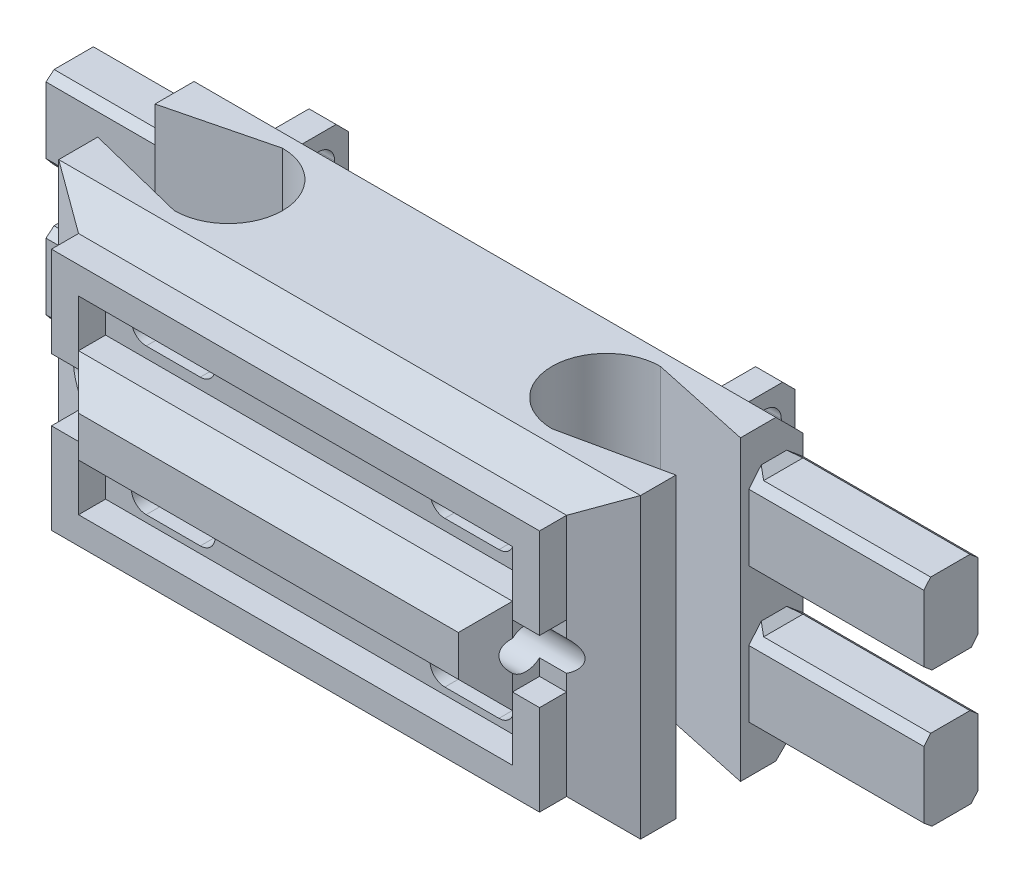
SolidWorks part; units mm, degrees
ref_plane "Front Plane" through (0, 0, 0) normal (0, 0, 1) x (1, 0, 0)
ref_plane "Top Plane" through (0, 0, 0) normal (0, 1, 0) x (1, 0, 0)
ref_plane "Right Plane" through (0, 0, 0) normal (1, 0, 0) x (0, 0, -1)
sketch "Base" plane through (0, 0, 0) normal (0, 0, 1) x (1, 0, 0)
  line L1 (0, 0) -> (21.5, 0)
  line L2 (0, 0) -> (0, 11)
  line L3 (0, 11) -> (21.5, 11)
  line L4 (21.5, 0) -> (21.5, 11)
  dimension "D1" = 21.5
  dimension "D2" = 11
extrude "Boss-Extrude1" add sketch "Base" along normal blind 7
chamfer "Chamfer4" distance 1 angle 45 2 edges at (10.75, 11, 7) (10.75, 0, 7)
chamfer "Chamfer5" distance 1 angle 60 2 edges at (0, 5.5, 7) (21.5, 5.5, 7)
chamfer "Chamfer6" distance 1 angle 45 2 edges at (10.75, 11, 0) (10.75, 0, 0)
sketch "Tendon extrude" plane through (0, 0, 0) normal (0, -1, 0) x (1, 0, 0)
  line L0 (10.75, 6) -> (10.75, -3.9632) construction
  line L1 (21.5, 6) -> (0, 6) construction
  line L2 (0, 3.5) -> (21.7648, 3.5) construction
  line L3 (0, 6) -> (0, 1) construction
  line L4 (3.77, 3.5) -> (-2.23, 3.5) construction
  line L5 (-2.23, 3) -> (-2.23, 4)
  line L6 (3.77, 5.5) -> (-2.23, 4)
  line L7 (-2.23, 3) -> (3.77, 1.5)
  line L10 (17.73, 3.5) -> (24.73, 3.5) construction
  line L11 (24.73, 3) -> (24.73, 4)
  line L12 (17.73, 5.5) -> (24.73, 4)
  line L13 (24.73, 3) -> (17.73, 1.5)
  circle A0 centre (3.77, 3.5) radius 2
  circle A1 centre (17.73, 3.5) radius 2
  dimension "D1" = 4
  dimension "D2" = 3.77
  dimension "D3" = 1
  dimension "D4" = 6
  dimension "D5" = 1
  dimension "D6" = 7
sketch "Sketch8" plane through (0, 0, 7) normal (0, 0, 1) x (1, 0, 0)
  line L0 (19.7679, 5.5) -> (1.7321, 5.5) construction
  line L1 (19.7679, 1) -> (19.7679, 10) construction
  line L2 (1.7321, 10) -> (1.7321, 1) construction
  line L3 (10.75, 1) -> (10.75, 10) construction
  line L4 (1.7321, 1) -> (19.7679, 1) construction
  line L5 (19.7679, 10) -> (1.7321, 10) construction
  line L6 (2.7321, 3.75) -> (2.7321, 7.25)
  line L7 (18.7679, 7.25) -> (2.7321, 7.25)
  line L8 (18.7679, 7.25) -> (18.7679, 3.75)
  line L9 (18.7679, 3.75) -> (2.7321, 3.75)
  point P17 (2.7321, 5.5)
  point P18 (18.7679, 5.5)
  dimension "D1" = 1.75
  dimension "D2" = 1
  dimension "D3" = 1
extrude "Boss-Extrude5" add sketch "Sketch8" along normal blind 2
sketch "Sketch9" plane through (18.7679, 0, 0) normal (1, 0, 0) x (0, 0, -1)
  line L0 (-9, 5.5) -> (-7, 5.5) construction
  line L1 (-9, 3.75) -> (-9, 7.25) construction
  line L2 (-7, 3.75) -> (-7, 7.25) construction
  circle A0 centre (-7.5, 5.5) radius 0.75
  dimension "D1" = 1.5
  dimension "D2" = 1.5
extrude "Cut-Extrude5" cut sketch "Sketch9" against normal blind 34.5 and the other way blind 4.2544
chamfer "Chamfer9" distance 1 angle 45 4 edges at (2.7321, 5.5, 9) (10.75, 7.25, 9) (18.7679, 5.5, 9) (10.75, 3.75, 9)
sketch "Sketch13" plane through (0, 0, 0) normal (0, 0, -1) x (-1, 0, 0)
  line L0 (0, 5.5) -> (-33.4926, 5.5) construction
  line L1 (0, 10) -> (0, 1) construction
  line L2 (-10.75, 1) -> (-10.75, 15.915) construction
  line L3 (-21.5, 1) -> (0, 1) construction
  line L4 (-1, 7.25) -> (-5.75, 7.25)
  line L5 (-15.75, 7.25) -> (-15.75, 3.75)
  line L6 (-1, 7.25) -> (-1, 3.75)
  line L7 (-1, 3.75) -> (-5.75, 3.75)
  line L8 (-5.75, 7.25) -> (-5.75, 3.75)
  line L9 (-20.5, 7.25) -> (-15.75, 7.25)
  line L10 (-20.5, 3.75) -> (-15.75, 3.75)
  line L11 (-20.5, 7.25) -> (-20.5, 3.75)
  point P13 (-5.75, 5.5)
  point P14 (-1, 5.5)
  dimension "D1" = 1.75
  dimension "D2" = 1
  dimension "D3" = 5
extrude "Boss-Extrude6" add sketch "Sketch13" along normal blind 2
chamfer "Chamfer10" distance 1 angle 45 8 edges at (15.75, 5.5, -2) (18.125, 3.75, -2) (20.5, 5.5, -2) (18.125, 7.25, -2) (3.375, 7.25, -2) (1, 5.5, -2) (3.375, 3.75, -2) (5.75, 5.5, -2)
sketch "Sketch14" plane through (1, 0, 0) normal (-1, 0, 0) x (0, 0, 1)
  line L0 (-1, 5.5) -> (0, 5.5) construction
  line L1 (-1, 7.25) -> (-1, 3.75) construction
  line L2 (0, 3.75) -> (0, 7.25) construction
  line L3 (-2, 4.75) -> (-2, 6.25) construction
  circle A0 centre (-0.5, 5.5) radius 0.75
  dimension "D1" = 1.5
  dimension "D2" = 1.5
extrude "Cut-Extrude6" cut sketch "Sketch14" against normal blind 30 and the other way blind 3
sketch "Sketch15" plane through (0, 0, 0) normal (0, 0, -1) x (-1, 0, 0)
  line L0 (-19.5, 4.75) -> (-16.75, 4.75) construction
  line L1 (-19.5, 1) -> (-18.5, 1)
  line L2 (-19.5, 1) -> (-19.5, 4.75)
  line L3 (-19.5, 4.75) -> (-18.5, 4.75)
  line L4 (-18.5, 1) -> (-18.5, 4.75)
  line L5 (-19.5, 6.25) -> (-19.5, 4.75) construction
  line L6 (-10.75, 1) -> (-10.75, 10) construction
  line L7 (-21.5, 1) -> (0, 1) construction
  line L8 (0, 10) -> (-21.5, 10) construction
  line L9 (-16.75, 6.25) -> (-19.5, 6.25) construction
  line L10 (-19.5, 6.25) -> (-18.5, 6.25)
  line L11 (-19.5, 6.25) -> (-19.5, 10)
  line L12 (-19.5, 10) -> (-18.5, 10)
  line L13 (-18.5, 6.25) -> (-18.5, 10)
  line L14 (-2, 1) -> (-3, 1)
  line L15 (-2, 1) -> (-2, 4.75)
  line L16 (-3, 1) -> (-3, 4.75)
  line L17 (-2, 4.75) -> (-3, 4.75)
  line L18 (-2, 6.25) -> (-3, 6.25)
  line L19 (-2, 10) -> (-3, 10)
  line L20 (-3, 6.25) -> (-3, 10)
  line L21 (-2, 6.25) -> (-2, 10)
  dimension "D1" = 0
  dimension "D3" = 1
  dimension "D4" = 0
  dimension "D5" = 0
extrude "Boss-Extrude7" add sketch "Sketch15" along normal blind 2
sketch "Sketch16" plane through (19.5, 0, 0) normal (1, 0, 0) x (0, 0, -1)
  line L0 (0.6, 3.15) -> (0.6, 2.15) construction
  line L1 (1.2, 3.15) -> (1.2, 2.15)
  line L2 (0, 3.15) -> (0, 2.15)
  line L3 (1, 3.75) -> (0, 3.75) construction
  line L5 (0.6, 7.85) -> (0.6, 8.85) construction
  line L6 (0, 7.85) -> (0, 8.85)
  line L7 (1.2, 7.85) -> (1.2, 8.85)
  line L9 (1, 7.25) -> (0, 7.25) construction
  line L10 (0, 3.75) -> (0, 1) construction
  arc A0 (1.2, 3.15) -> (0, 3.15) centre (0.6, 3.15) ccw
  arc A1 (0, 2.15) -> (1.2, 2.15) centre (0.6, 2.15) ccw
  arc A2 (0, 7.85) -> (1.2, 7.85) centre (0.6, 7.85) ccw
  arc A3 (1.2, 8.85) -> (0, 8.85) centre (0.6, 8.85) ccw
  point P2 (0.6, 2.65)
  point P13 (0.6, 8.35)
  point P20 (0.5, 7.25)
  dimension "D1" = 1
  dimension "D2" = 0.6
  dimension "D3" = 0.6
  dimension "D4" = 0
  dimension "D5" = 0.6
extrude "Cut-Extrude7" cut sketch "Sketch16" against normal blind 26
chamfer "Chamfer11" distance 0.3 angle 45 8 edges at (2, 2.875, -2) (3, 2.875, -2) (3, 8.125, -2) (2, 8.125, -2) (19.5, 8.125, -2) (18.5, 8.125, -2) (19.5, 2.875, -2) (18.5, 2.875, -2)
chamfer "Chamfer12" distance 0.75 angle 45 4 edges at (19, 1, -2) (19, 10, -2) (2.5, 10, -2) (2.5, 1, -2)
extrude "Cut-Extrude8" cut sketch "Tendon extrude" against normal up to surface (11 mm away)
sketch "Sketch18" plane through (21.5, 0, 0) normal (1, 0, 0) x (0, 0, -1)
  line L0 (-2.3079, 5.5) -> (-0.25, 5.5) construction
  line L1 (-2.3079, 11) -> (-2.3079, 0) construction
  line L3 (-2, 6.5) -> (0, 6.5)
  line L4 (-2, 6.5) -> (-2, 9.5)
  line L5 (-2, 9.5) -> (0, 9.5)
  line L6 (0, 6.5) -> (0, 9.5)
  line L7 (-2, 4.5) -> (0, 4.5)
  line L8 (0, 4.5) -> (0, 1.5)
  line L9 (-2, 1.5) -> (0, 1.5)
  line L10 (-2, 4.5) -> (-2, 1.5)
  line L11 (0, 6.059) -> (0, 10) construction
  arc A0 (0, 6.059) -> (0, 4.941) centre (0.5, 5.5) ccw construction
  dimension "D1" = 3
  dimension "D2" = 2
  dimension "D3" = 1
extrude "Boss-Extrude8" add sketch "Sketch18" along normal blind 6.47
chamfer "Chamfer13" distance 0.25 angle 50 8 edges at (24.735, 1.5, 2) (24.735, 4.5, 2) (24.735, 6.5, 2) (24.735, 9.5, 2) (24.735, 9.5, 0) (24.735, 6.5, 0) (24.735, 4.5, 0) (24.735, 1.5, 0)
chamfer "Chamfer14" distance 0.25 angle 50 4 edges at (21.5, 9.5, 1.024) (21.5, 1.5, 0.976) (21.5, 4.5, 1.024) (21.5, 6.5, 0.976)
sketch "Sketch19" plane through (0, 0, 0) normal (-1, 0, 0) x (0, 0, 1)
  line L0 (0.25, 5.5) -> (2.4425, 5.5) construction
  line L1 (2.4425, 11) -> (2.4425, 0) construction
  line L3 (0, 4.5) -> (2, 4.5)
  line L4 (0, 4.5) -> (0, 1.5)
  line L5 (0, 1.5) -> (2, 1.5)
  line L6 (2, 4.5) -> (2, 1.5)
  line L7 (2, 6.5) -> (2, 9.5)
  line L8 (0, 9.5) -> (2, 9.5)
  line L9 (0, 6.5) -> (0, 9.5)
  line L10 (0, 6.5) -> (2, 6.5)
  line L11 (0, 4.941) -> (0, 1) construction
  arc A0 (0, 4.941) -> (0, 6.059) centre (-0.5, 5.5) ccw construction
  dimension "D1" = 2
  dimension "D2" = 3
  dimension "D4" = 1
extrude "Boss-Extrude9" add sketch "Sketch19" along normal blind 4.47
chamfer "Chamfer15" distance 0.25 angle 50 8 edges at (-2.235, 1.5, 2) (-2.235, 4.5, 2) (-2.235, 9.5, 2) (-2.235, 6.5, 2) (-2.235, 1.5, 0) (-2.235, 4.5, 0) (-2.235, 9.5, 0) (-2.235, 6.5, 0)
chamfer "Chamfer16" distance 0.25 angle 50 4 edges at (0, 9.5, 0.976) (0, 6.5, 1.024) (0, 4.5, 0.976) (0, 1.5, 1.024)
sketch "Sketch20" plane through (0, 0, 7) normal (0, 0, 1) x (1, 0, 0)
  line L0 (19.7679, 6.059) -> (19.7679, 10) construction
  line L1 (1.7321, 10) -> (19.7679, 10)
  line L2 (1.7321, 10) -> (1.7321, 9)
  line L3 (1.7321, 9) -> (19.7679, 9)
  line L4 (19.7679, 10) -> (19.7679, 9)
  line L5 (2.7321, 7.25) -> (2.7321, 6.059) construction
  line L6 (2.7321, 6.6545) -> (1.7321, 6.6545)
  line L7 (2.7321, 6.6545) -> (2.7321, 9)
  line L8 (2.7321, 9) -> (1.7321, 9)
  line L9 (1.7321, 6.6545) -> (1.7321, 9)
  line L10 (18.7679, 6.059) -> (18.7679, 7.25) construction
  line L11 (18.7679, 6.6545) -> (19.7679, 6.6545)
  line L12 (18.7679, 6.6545) -> (18.7679, 9)
  line L13 (18.7679, 9) -> (19.7679, 9)
  line L14 (19.7679, 6.6545) -> (19.7679, 9)
  line L15 (1.7321, 4.941) -> (1.7321, 1) construction
  line L16 (19.7679, 1) -> (1.7321, 1)
  line L17 (19.7679, 1) -> (19.7679, 2)
  line L18 (19.7679, 2) -> (1.7321, 2)
  line L19 (1.7321, 1) -> (1.7321, 2)
  line L20 (2.7321, 4.941) -> (2.7321, 3.75) construction
  line L21 (2.7321, 4.3455) -> (1.7321, 4.3455)
  line L22 (2.7321, 4.3455) -> (2.7321, 2)
  line L23 (2.7321, 2) -> (1.7321, 2)
  line L24 (1.7321, 4.3455) -> (1.7321, 2)
  line L25 (18.7679, 3.75) -> (18.7679, 4.941) construction
  line L26 (19.7679, 2) -> (18.7679, 2)
  line L27 (19.7679, 2) -> (19.7679, 4.3455)
  line L28 (19.7679, 4.3455) -> (18.7679, 4.3455)
  line L29 (18.7679, 2) -> (18.7679, 4.3455)
  line M2 (19.7679, 6.059) -> (19.7679, 10)
  line M3 (19.7679, 10) -> (1.7321, 10)
  line M4 (1.7321, 10) -> (1.7321, 6.059)
  line M6 (2.7321, 6.059) -> (2.7321, 7.25)
  line M8 (18.7679, 7.25) -> (18.7679, 6.059)
extrude "Boss-Extrude10" add sketch "Sketch20" along normal blind 1 contours L7 L3 L6 M6 M4 | L3 M4 M2 M3 | L12 L11 L3 M8 M2 | L29 L18 L27 L28 | L19 L16 L17 L18 | L21 L24 L18 L22
sketch "Sketch21" plane through (0, 0, 7) normal (0, 0, 1) x (1, 0, 0)
  line L0 (4.2321, 8.2) -> (6.2321, 8.2) construction
  line L1 (4.2321, 8.7469) -> (6.2321, 8.7469)
  line L2 (4.2321, 7.6531) -> (6.2321, 7.6531)
  line L3 (15.2679, 8.2) -> (17.2679, 8.2) construction
  line L4 (15.2679, 8.7469) -> (17.2679, 8.7469)
  line L5 (15.2679, 7.6531) -> (17.2679, 7.6531)
  line L6 (15.2679, 2.8) -> (17.2679, 2.8) construction
  line L7 (15.2679, 3.3469) -> (17.2679, 3.3469)
  line L8 (15.2679, 2.2531) -> (17.2679, 2.2531)
  line L9 (6.2321, 2.8) -> (4.2321, 2.8) construction
  line L10 (6.2321, 2.2531) -> (4.2321, 2.2531)
  line L11 (6.2321, 3.3469) -> (4.2321, 3.3469)
  line L12 (2.7321, 9) -> (18.7679, 9) construction
  line L13 (18.7679, 2) -> (2.7321, 2) construction
  line L14 (2.7321, 7.25) -> (2.7321, 9) construction
  line L15 (18.7679, 7.25) -> (18.7679, 9) construction
  arc A0 (4.2321, 8.7469) -> (4.2321, 7.6531) centre (4.2321, 8.2) ccw
  arc A1 (6.2321, 7.6531) -> (6.2321, 8.7469) centre (6.2321, 8.2) ccw
  arc A2 (15.2679, 8.7469) -> (15.2679, 7.6531) centre (15.2679, 8.2) ccw
  arc A3 (17.2679, 7.6531) -> (17.2679, 8.7469) centre (17.2679, 8.2) ccw
  arc A4 (15.2679, 3.3469) -> (15.2679, 2.2531) centre (15.2679, 2.8) ccw
  arc A5 (17.2679, 2.2531) -> (17.2679, 3.3469) centre (17.2679, 2.8) ccw
  arc A6 (6.2321, 2.2531) -> (6.2321, 3.3469) centre (6.2321, 2.8) ccw
  arc A7 (4.2321, 3.3469) -> (4.2321, 2.2531) centre (4.2321, 2.8) ccw
  point P2 (5.2321, 8.2)
  point P7 (16.2679, 8.2)
  point P14 (16.2679, 2.8)
  point P21 (5.2321, 2.8)
  point P32 (2.7321, 8.125)
  point P35 (18.7679, 8.125)
  dimension "D1" = 0.8
  dimension "D2" = 0.8
  dimension "D3" = 2
  dimension "D4" = 1.5
  dimension "D5" = 1.5
extrude "Cut-Extrude9" cut sketch "Sketch21" against normal blind 1
